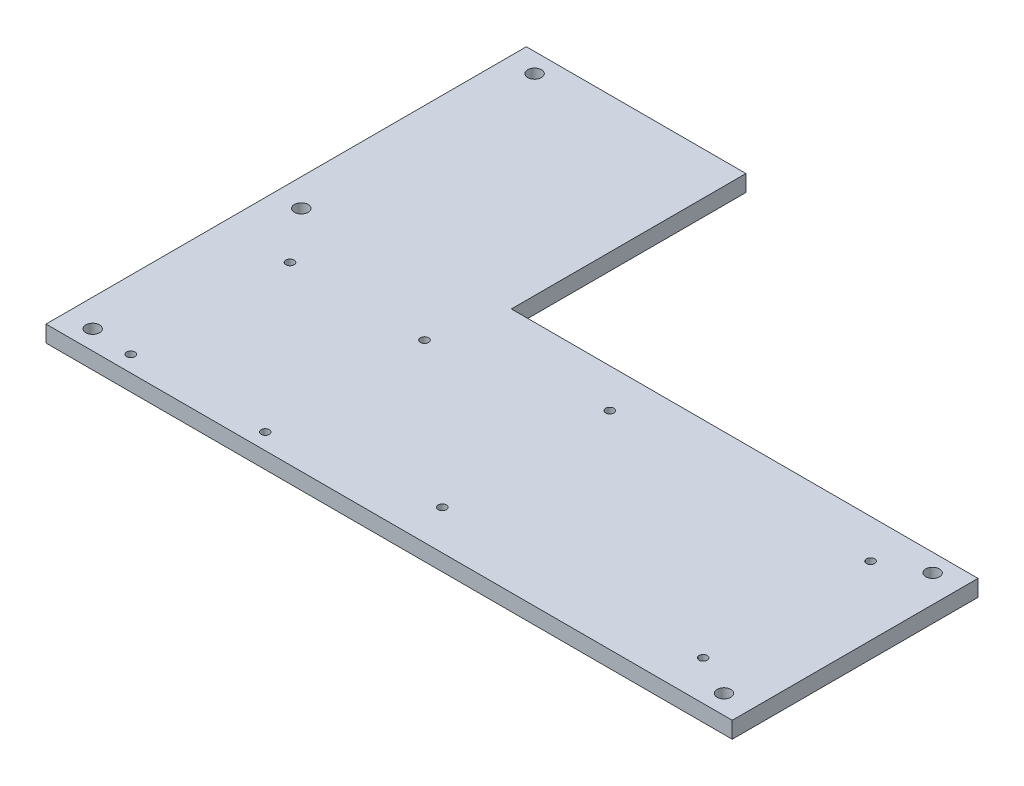
SolidWorks part; units mm, degrees
ref_plane "Front Plane" through (0, 0, 0) normal (0, 0, 1) x (1, 0, 0)
ref_plane "Top Plane" through (0, 0, 0) normal (0, 1, 0) x (1, 0, 0)
ref_plane "Right Plane" through (0, 0, 0) normal (1, 0, 0) x (0, 0, -1)
sketch "Sketch1" plane through (0, 0, 0) normal (0, 1, 0) x (1, 0, 0)
  line L0 (-125.3239, 45.1167) -> (-125.3239, 130.1167)
  line L1 (-125.3239, 130.1167) -> (-45.3239, 130.1167)
  line L2 (-125.3239, 45.1167) -> (-125.3239, -44.8833)
  line L3 (-125.3239, -44.8833) -> (124.6756, -44.8833)
  line L4 (124.6756, 44.6511) -> (124.6756, -44.8833)
  line L5 (-125.3239, 45.1167) -> (124.6756, -44.8833) construction
  line L6 (-125.3239, -44.8833) -> (124.6756, 44.6511) construction
  line L7 (-100.3239, -39) -> (-51.3239, -39) construction
  line L8 (-100.3239, -39) -> (-100.3239, 19) construction
  line L9 (-100.3239, 19) -> (-51.3239, 19) construction
  line L10 (-51.3239, -39) -> (-51.3239, 19) construction
  line L11 (-100.3239, -39) -> (-51.3239, 19) construction
  line L12 (-100.3239, 19) -> (-51.3239, -39) construction
  line L13 (4.6756, -30.5) -> (99.6756, -30.5) construction
  line L14 (4.6756, -30.5) -> (4.6756, 30.5) construction
  line L15 (4.6756, 30.5) -> (99.6756, 30.5) construction
  line L16 (99.6756, -30.5) -> (99.6756, 30.5) construction
  line L17 (4.6756, -30.5) -> (99.6756, 30.5) construction
  line L18 (4.6756, 30.5) -> (99.6756, -30.5) construction
  line L19 (-45.3239, 130.1167) -> (-45.3239, 44.6511)
  line L20 (-45.3239, 44.6511) -> (124.6756, 44.6511)
  circle A0 centre (-100.3239, 19) radius 1.5
  circle A1 centre (-51.3239, 19) radius 1.5
  circle A2 centre (-51.3239, -39) radius 1.5
  circle A3 centre (-100.3239, -39) radius 1.5
  circle A4 centre (4.6756, 30.5) radius 1.5
  circle A5 centre (99.6756, 30.5) radius 1.5
  circle A6 centre (99.6756, -30.5) radius 1.5
  circle A7 centre (4.6756, -30.5) radius 1.5
  circle A8 centre (-115.3239, 38.1167) radius 2.5
  circle A9 centre (-115.3239, -37.8833) radius 2.5
  circle A10 centre (114.6756, -37.8833) radius 2.5
  circle A11 centre (114.6756, 38.1167) radius 2.5
  circle A12 centre (-115.3239, 123.1167) radius 2.5
  point P0 (0, 0)
  point P6 (-75.8239, -10)
  point P16 (52.1756, 0)
  dimension "D6" = 3
  dimension "D10" = 3
  dimension "D5" = 25
  dimension "D13" = 5
  dimension "D17" = 7
  dimension "D1" = 90
  dimension "D2" = 250
  dimension "D3" = 49
  dimension "D4" = 58
  dimension "D7" = 25
  dimension "D8" = 61
  dimension "D9" = 95
  dimension "D11" = 10
  dimension "D12" = 80
  dimension "D14" = 10
  dimension "D15" = 7
  dimension "D16" = 85
  dimension "D18" = 10
  dimension "D19" = 7
extrude "Boss-Extrude1" add sketch "Sketch1" along normal blind 6 contours L4 L3 L2 L0 L1 L19 L20
extrude "Cut-Extrude1" cut sketch "Sketch1<3>" along normal blind 6 contours A3 | A2 | A1 | A0 | A12
sketch "Sketch1<3>" plane through (0, 0, 0) normal (0, 1, 0) x (1, 0, 0) same geometry as "Sketch1"
extrude "Cut-Extrude3" cut sketch "Sketch1<4>" along normal blind 6 contours A4 | A5 | A6 | A7 | A8 | A9 | A10 | A11
sketch "Sketch1<4>" plane through (0, 0, 0) normal (0, 1, 0) x (1, 0, 0) same geometry as "Sketch1"
